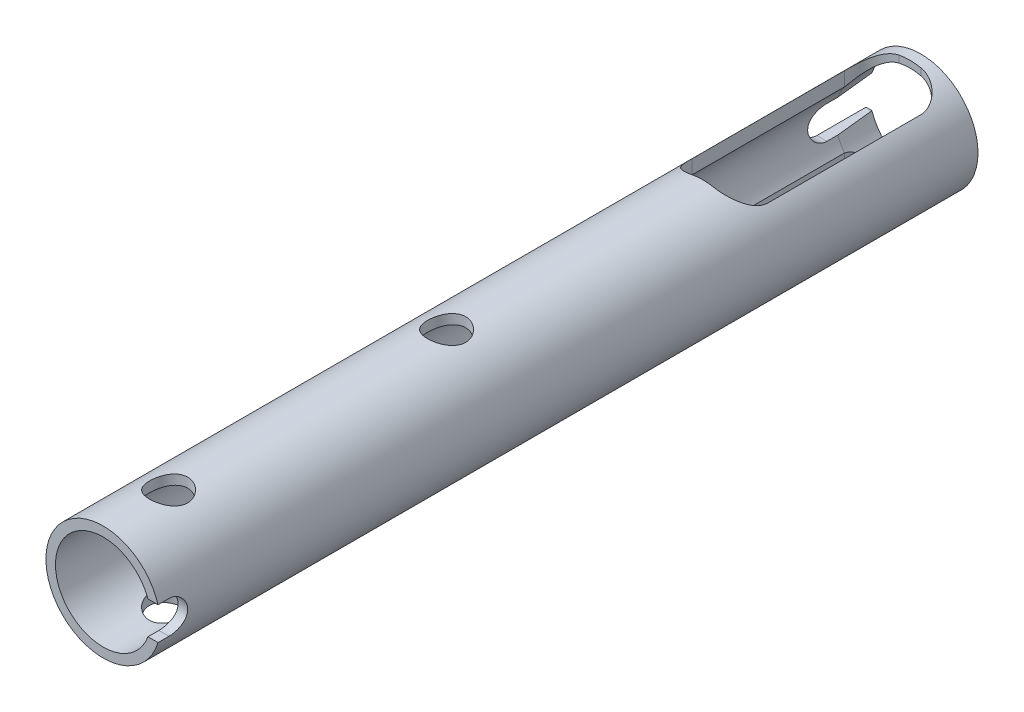
SolidWorks part; units mm, degrees
material "6061 合金"
ref_plane "前视" through (0, 0, 0) normal (0, 0, 1) x (1, 0, 0)
ref_plane "上视" through (0, 0, 0) normal (0, 1, 0) x (1, 0, 0)
ref_plane "右视" through (0, 0, 0) normal (1, 0, 0) x (0, 0, -1)
sketch "草图1" plane through (0, 0, 0) normal (0, 0, 1) x (1, 0, 0)
  circle A0 centre (0, 0) radius 10.5
  circle A1 centre (0, 0) radius 8.75
  dimension "D1" = 17.5
  dimension "D2" = 21
extrude "凸台-拉伸1" add sketch "草图1" along normal blind 150
chamfer "倒角1" distance 7 distance2 0.7 1 edges at (8.75, 0, 0) first distance on face at (8.75, 0, 150)
sketch "草图4" plane through (0, 0, 0) normal (0, 1, 0) x (1, 0, 0)
  line L0 (0, 0) -> (0, -21) construction
  line L2 (-7, -2) -> (7, -2)
  line L3 (-7, -2) -> (-7, -40)
  line L4 (-7, -40) -> (7, -40)
  line L5 (7, -2) -> (7, -40)
  line L6 (-7, -2) -> (7, -40) construction
  line L7 (-7, -40) -> (7, -2) construction
  line L9 (10.5, 0) -> (-10.5, 0) construction
  dimension "37" = 21
  dimension "D2" = 38
  dimension "D3" = 14
extrude "切除-拉伸1" cut sketch "草图4" against normal mid plane 180
fillet "圆角1" radius 5 8 edges at (-7, -6.5381, 40) (7, -6.9365, 2) (7, -6.5381, 40) (-7, -6.9365, 2) (7, 6.5381, 40) (-7, 6.5381, 40) (7, 6.9365, 2) (-7, 6.9365, 2)
sketch "草图5" plane through (0, 0, 0) normal (1, 0, 0) x (0, -1, 0)
  line L0 (0, -150) -> (0, -148) construction
  line L1 (-10.5, -150) -> (10.5, -150) construction
  line L2 (0, -150) -> (0, -148) construction
  line L3 (-3, -150) -> (-3, -148)
  line L4 (3, -150) -> (3, -148)
  arc A0 (-3, -150) -> (3, -150) centre (0, -150) ccw
  arc A1 (3, -148) -> (-3, -148) centre (0, -148) ccw
  point P5 (0, -149)
  dimension "D1" = 3
  dimension "D2" = 2
extrude "切除-拉伸2" cut sketch "草图5" along normal blind 15
sketch "草图6" plane through (0, 0, 0) normal (0, 1, 0) x (1, 0, 0)
  line L0 (0, -162) -> (0, -87) construction
  line L1 (-10.5, -150) -> (10.0623, -150) construction
  circle A0 centre (0, -87) radius 3.5
  circle A1 centre (0, -138) radius 3.5
  dimension "D1" = 7
  dimension "D2" = 12
  dimension "D3" = 63
extrude "切除-拉伸3" cut sketch "草图6" against normal mid plane 30
sketch "草图16" plane through (0, 0, 0) normal (1, 0, 0) x (0, 0, -1)
  line L0 (-9, 0) -> (-4, 0) construction
  line L1 (-9, 3) -> (0, 3)
  line L2 (-9, -3) -> (0, -3)
  line L3 (0, -10.5) -> (0, 10.5) construction
  line L5 (0, -10.5) -> (0, 10.5) construction
  line L6 (0, -3) -> (0, 3)
  arc A0 (-9, 3) -> (-9, -3) centre (-9, 0) ccw
  point P2 (-7, 0)
  dimension "D3" = 6
  dimension "D1" = 4
  dimension "D2" = 5
extrude "切除-拉伸10" cut sketch "草图16" against normal blind 22
